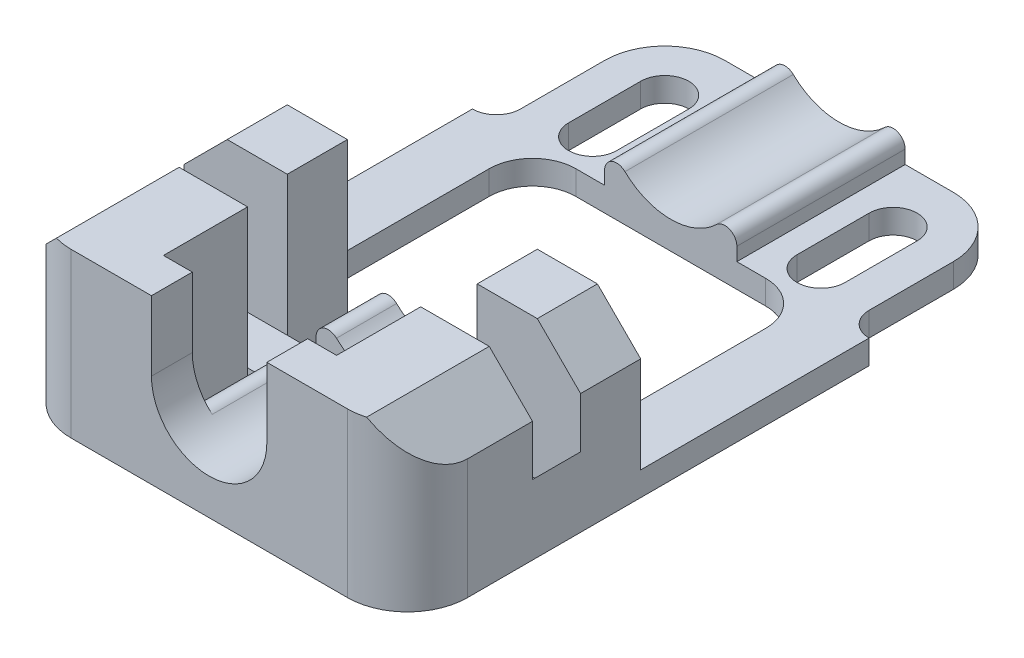
SolidWorks part; units mm, degrees
ref_plane "Front Plane" through (0, 0, 0) normal (0, 0, 1) x (1, 0, 0)
ref_plane "Top Plane" through (0, 0, 0) normal (0, 1, 0) x (1, 0, 0)
ref_plane "Right Plane" through (0, 0, 0) normal (1, 0, 0) x (0, 0, -1)
sketch "Sketch1" plane through (0, 0, 0) normal (0, 1, 0) x (1, 0, 0)
  line L1 (-8.25, 4.85) -> (8.25, 4.85)
  line L2 (-8.25, 4.85) -> (-8.25, -4.85)
  line L3 (-8.25, -4.85) -> (8.25, -4.85)
  line L4 (8.25, 4.85) -> (8.25, -4.85)
  line L5 (-8.25, 4.85) -> (8.25, -4.85) construction
  line L6 (-8.25, -4.85) -> (8.25, 4.85) construction
  point P0 (0, 0)
  dimension "D1" = 16.5
  dimension "D2" = 9.7
extrude "Boss-Extrude1" add sketch "Sketch1" along normal blind 6.8
sketch "Sketch2" plane through (0, 6.8, 0) normal (0, 1, 0) x (1, 0, 0)
  line L0 (-8.25, 1.35) -> (8.25, 1.35) construction
  line L3 (-8.25, 4.85) -> (-8.25, -4.85) construction
  line L4 (-8.25, 2.35) -> (8.25, 2.35)
  line L5 (-8.25, 2.35) -> (-8.25, 0.35)
  line L6 (-8.25, 0.35) -> (8.25, 0.35)
  line L7 (8.25, 2.35) -> (8.25, 0.35)
  line L8 (-8.25, 2.35) -> (8.25, 0.35) construction
  line L9 (-8.25, 0.35) -> (8.25, 2.35) construction
  line L10 (8.25, -4.85) -> (8.25, 4.85) construction
  line L11 (8.25, 4.85) -> (-8.25, 4.85) construction
  line L12 (0, 4.85) -> (0, -4.85) construction
  line L13 (-8.25, -4.85) -> (8.25, -4.85) construction
  point P6 (0, 1.35)
  dimension "D1" = 16.5
  dimension "D2" = 2
  dimension "D3" = 2.5
extrude "Cut-Extrude1" cut sketch "Sketch2" against normal blind 5.8
sketch "Sketch3" plane through (0, 0, -4.85) normal (0, 0, -1) x (-1, 0, 0)
  line L0 (0, 6.8) -> (0, 0) construction
  line L1 (-8.25, 6.8) -> (8.25, 6.8) construction
  line L2 (-8.25, 0) -> (8.25, 0) construction
  line L3 (-8.25, 1) -> (8.25, 1) construction
  line L4 (-8.25, 6.8) -> (-8.25, 0) construction
  line L5 (8.25, 6.8) -> (8.25, 0) construction
  line L6 (-8.25, 1) -> (8.25, 1) construction
  line L7 (-8.25, 6.8) -> (8.25, 1) construction
  line L8 (8.25, 6.8) -> (-8.25, 1) construction
  line L9 (-2.75, 3.9) -> (-2.75, 6.8)
  line L10 (2.75, 3.9) -> (2.75, 6.8)
  circle A0 centre (0, 3.9) radius 2.75
  line M5 (8.25, 6.8) -> (-8.25, 6.8)
  dimension "D1" = 5.5
extrude "Cut-Extrude2" cut sketch "Sketch3" against normal up to next contours A0 | A0 L10 L9 M5 region at (2.6878, 5.35, -4.85) region at (0, 3.9, -4.85)
sketch "Sketch4" plane through (0, 0, 4.85) normal (0, 0, 1) x (1, 0, 0)
  line L0 (0, 0) -> (0, 6.8) construction
  line L1 (-8.25, 6.8) -> (8.25, 6.8) construction
  line L3 (-2.4, 3.9) -> (2.4, 3.9)
  line L4 (-2.4, 3.9) -> (-2.4, 6.8)
  line L5 (-2.4, 6.8) -> (2.4, 6.8)
  line L6 (2.4, 3.9) -> (2.4, 6.8)
  circle A0 centre (0, 3.9) radius 2.4
  arc A1 (-2.75, 3.9) -> (2.75, 3.9) centre (0, 3.9) ccw construction
  line M4 (8.25, 6.8) -> (-8.25, 6.8)
  dimension "D1" = 4.8
extrude "Cut-Extrude3" cut sketch "Sketch4" against normal up to next contours L0 A0 L3 | A0 L0 L3 | L3 L0 A0 | L0 L3 A0 | L0 A0 L6 M4 | A0 L0 L5 L4 region at (-1.0186, 2.8814, 4.85) region at (1.0186, 2.8814, 4.85) region at (-1.0186, 4.9186, 4.85) region at (1.0186, 4.9186, 4.85) region at (-1.5369, 6.1511, 4.85) region at (1.5369, 6.1511, 4.85)
sketch "Sketch5" plane through (0, 6.8, 0) normal (0, 1, 0) x (1, 0, 0)
  line L0 (-2.75, 2.35) -> (-8.25, 2.35) construction
  line L1 (-2.75, 4.85) -> (-3.95, 4.85)
  line L2 (-2.75, 4.85) -> (-2.75, 2.35)
  line L3 (-2.75, 2.35) -> (-3.95, 2.35)
  line L4 (-3.95, 4.85) -> (-3.95, 2.35)
  line L5 (8.25, 2.35) -> (2.75, 2.35) construction
  line L6 (2.75, 4.85) -> (3.95, 4.85)
  line L7 (2.75, 4.85) -> (2.75, 2.35)
  line L8 (2.75, 2.35) -> (3.95, 2.35)
  line L9 (3.95, 4.85) -> (3.95, 2.35)
  line L11 (-2.4, 0.35) -> (-3.6, 0.35)
  line L12 (-2.4, 0.35) -> (-2.4, -3.15)
  line L13 (-2.4, -3.15) -> (-3.6, -3.15)
  line L14 (-3.6, 0.35) -> (-3.6, -3.15)
  line L15 (2.4, 0.35) -> (3.6, 0.35)
  line L16 (2.4, 0.35) -> (2.4, -3.15)
  line L17 (2.4, -3.15) -> (3.6, -3.15)
  line L18 (3.6, 0.35) -> (3.6, -3.15)
  dimension "D1" = 1.2
  dimension "D2" = 3.5
extrude "Cut-Extrude4" cut sketch "Sketch5" against normal through all
sketch "Sketch6" plane through (0, 6.8, 0) normal (0, 1, 0) x (1, 0, 0)
  line L1 (-8.25, -4.85) -> (8.25, -4.85)
  line L2 (-8.25, -4.85) -> (-8.25, 4.85)
  line L3 (-8.25, 4.85) -> (8.25, 4.85)
  line L4 (8.25, -4.85) -> (8.25, 4.85)
extrude "Cut-Extrude5" [suppressed] cut sketch "Sketch6" against normal up to vertex up to point (2.4, 3.9, 3.15)
sketch "Sketch7" plane through (0, 0, -2.35) normal (0, 0, 1) x (1, 0, 0)
  line L0 (-6.35, 1) -> (-8.25, 2.9)
  line L1 (-3.95, 1) -> (-8.25, 1) construction
  line L2 (-8.25, 1) -> (-8.25, 6.8) construction
  line L3 (0, 0) -> (0, 3.9) construction
  line L4 (-8.25, 2.9) -> (-8.25, 1)
  line L5 (-8.25, 6.8) -> (-8.25, 0) construction
  line L6 (-8.25, 1) -> (-6.35, 1)
  line L7 (8.25, 2.9) -> (8.25, 1)
  line L8 (6.35, 1) -> (8.25, 2.9)
  line L9 (8.25, 1) -> (6.35, 1)
  dimension "D1" = 45
  dimension "D2" = 1.9
extrude "Boss-Extrude2" add sketch "Sketch7" along normal up to surface (2 mm away) up to face at (-5.925, 3.9, -0.35)
chamfer "Chamfer1" distance 1.8 angle 45 4 edges at (-8.25, 6.8, -3.6) (-8.25, 6.8, 2.25) (8.25, 6.8, -3.6) (8.25, 6.8, 2.25)
fillet "Fillet4" radius 2.5 2 edges at (8.25, 2.5, 4.85) (-8.25, 2.5, 4.85)
sketch "Sketch8" plane through (0, 0, 0) normal (0, -1, 0) x (1, 0, 0)
  line L0 (-5.75, -18.85) -> (-5.75, -15.85) construction
  line L1 (-3.75, -15.85) -> (-3.75, -18.85) construction
  line L2 (5.75, -18.85) -> (5.75, -15.85) construction
  line L3 (3.75, -15.85) -> (3.75, -18.85) construction
  line L4 (-5.75, -18.85) -> (-5.75, -15.85)
  line L5 (-3.75, -15.85) -> (-3.75, -18.85)
  line L6 (5.75, -18.85) -> (5.75, -15.85)
  line L7 (3.75, -15.85) -> (3.75, -18.85)
  line L8 (-8.25, -4.85) -> (-8.25, -14.35)
  line L9 (8.25, -4.85) -> (8.25, -14.35)
  line L10 (-8.25, -14.35) -> (8.25, -14.35)
  line L11 (-8.25, -4.85) -> (-5.75, -4.85)
  line L12 (78.5, 13.6414) -> (78.5, 114.6586)
  line L13 (48.9288, -14.35) -> (50.5086, -14.35)
  line L14 (45.9288, -15.35) -> (47.9288, -15.35)
  line L15 (8.25, -14.35) -> (44.9288, -14.35)
  line L16 (7.25, -18.85) -> (7.25, -15.35)
  line L17 (-4.75, -21.35) -> (4.75, -21.35)
  line L18 (-7.25, -15.35) -> (-7.25, -18.85)
  line L19 (-44.9288, -14.35) -> (-8.25, -14.35)
  line L20 (-47.9288, -15.35) -> (-45.9288, -15.35)
  line L21 (-50.5086, -14.35) -> (-48.9288, -14.35)
  line L22 (-78.5, 114.6586) -> (-78.5, 13.6414)
  line L23 (50.5086, 142.65) -> (-50.5086, 142.65)
  line L24 (78.5, 13.6414) -> (78.5, 114.6586)
  line L25 (48.9288, -14.35) -> (50.5086, -14.35)
  line L26 (45.9288, -15.35) -> (47.9288, -15.35)
  line L27 (8.25, -14.35) -> (44.9288, -14.35)
  line L28 (7.25, -18.85) -> (7.25, -15.35)
  line L29 (-4.75, -21.35) -> (4.75, -21.35)
  line L30 (-7.25, -15.35) -> (-7.25, -18.85)
  line L31 (-44.9288, -14.35) -> (-8.25, -14.35)
  line L32 (-47.9288, -15.35) -> (-45.9288, -15.35)
  line L33 (-50.5086, -14.35) -> (-48.9288, -14.35)
  line L34 (-78.5, 114.6586) -> (-78.5, 13.6414)
  line L35 (50.5086, 142.65) -> (-50.5086, 142.65)
  line L36 (-8.25, -4.85) -> (-8.25, -15.85)
  line L37 (-8.25, -15.85) -> (-5.75, -15.85)
  line L38 (-5.75, -4.85) -> (-5.75, -15.85)
  line L39 (8.25, -4.85) -> (5.75, -4.85)
  line L40 (8.25, -4.85) -> (8.25, -15.85)
  line L41 (8.25, -15.85) -> (5.75, -15.85)
  line L42 (5.75, -4.85) -> (5.75, -15.85)
  arc A0 (-5.75, -18.85) -> (-3.75, -18.85) centre (-4.75, -18.85) ccw construction
  arc A1 (-3.75, -15.85) -> (-5.75, -15.85) centre (-4.75, -15.85) ccw construction
  arc A2 (3.75, -18.85) -> (5.75, -18.85) centre (4.75, -18.85) ccw construction
  arc A3 (5.75, -15.85) -> (3.75, -15.85) centre (4.75, -15.85) ccw construction
  arc A4 (-5.75, -18.85) -> (-3.75, -18.85) centre (-4.75, -18.85) ccw
  arc A5 (-3.75, -15.85) -> (-5.75, -15.85) centre (-4.75, -15.85) ccw
  arc A6 (3.75, -18.85) -> (5.75, -18.85) centre (4.75, -18.85) ccw
  arc A7 (5.75, -15.85) -> (3.75, -15.85) centre (4.75, -15.85) ccw
  arc A20 (78.7927, 115.3655) -> (51.2155, 142.9427) centre (65, 129.15) ccw
  arc A21 (78.7927, 115.3655) -> (78.5, 114.6586) centre (79.5, 114.6586) ccw
  arc A22 (78.5, 13.6414) -> (78.7927, 12.9345) centre (79.5, 13.6414) ccw
  arc A23 (51.2155, -14.6427) -> (78.7927, 12.9345) centre (65, -0.85) ccw
  arc A24 (51.2155, -14.6427) -> (50.5086, -14.35) centre (50.5086, -15.35) ccw
  arc A25 (48.9288, -14.35) -> (47.9288, -15.35) centre (48.9288, -15.35) ccw
  arc A26 (45.9288, -15.35) -> (44.9288, -14.35) centre (44.9288, -15.35) ccw
  arc A27 (8.25, -14.35) -> (7.25, -15.35) centre (8.25, -15.35) ccw
  arc A28 (4.75, -21.35) -> (7.25, -18.85) centre (4.75, -18.85) ccw
  arc A29 (-7.25, -18.85) -> (-4.75, -21.35) centre (-4.75, -18.85) ccw
  arc A30 (-7.25, -15.35) -> (-8.25, -14.35) centre (-8.25, -15.35) ccw
  arc A31 (-44.9288, -14.35) -> (-45.9288, -15.35) centre (-44.9288, -15.35) ccw
  arc A32 (-47.9288, -15.35) -> (-48.9288, -14.35) centre (-48.9288, -15.35) ccw
  arc A33 (-50.5086, -14.35) -> (-51.2155, -14.6427) centre (-50.5086, -15.35) ccw
  arc A34 (-78.7927, 12.9345) -> (-51.2155, -14.6427) centre (-65, -0.85) ccw
  arc A35 (-78.7927, 12.9345) -> (-78.5, 13.6414) centre (-79.5, 13.6414) ccw
  arc A36 (-78.5, 114.6586) -> (-78.7927, 115.3655) centre (-79.5, 114.6586) ccw
  arc A37 (-51.2155, 142.9427) -> (-78.7927, 115.3655) centre (-65, 129.15) ccw
  arc A38 (-51.2155, 142.9427) -> (-50.5086, 142.65) centre (-50.5086, 143.65) ccw
  arc A39 (50.5086, 142.65) -> (51.2155, 142.9427) centre (50.5086, 143.65) ccw
  arc A40 (78.7927, 115.3655) -> (51.2155, 142.9427) centre (65, 129.15) ccw
  arc A41 (78.7927, 115.3655) -> (78.5, 114.6586) centre (79.5, 114.6586) ccw
  arc A42 (78.5, 13.6414) -> (78.7927, 12.9345) centre (79.5, 13.6414) ccw
  arc A43 (51.2155, -14.6427) -> (78.7927, 12.9345) centre (65, -0.85) ccw
  arc A44 (51.2155, -14.6427) -> (50.5086, -14.35) centre (50.5086, -15.35) ccw
  arc A45 (48.9288, -14.35) -> (47.9288, -15.35) centre (48.9288, -15.35) ccw
  arc A46 (45.9288, -15.35) -> (44.9288, -14.35) centre (44.9288, -15.35) ccw
  arc A47 (8.25, -14.35) -> (7.25, -15.35) centre (8.25, -15.35) ccw
  arc A48 (4.75, -21.35) -> (7.25, -18.85) centre (4.75, -18.85) ccw
  arc A49 (-7.25, -18.85) -> (-4.75, -21.35) centre (-4.75, -18.85) ccw
  arc A50 (-7.25, -15.35) -> (-8.25, -14.35) centre (-8.25, -15.35) ccw
  arc A51 (-44.9288, -14.35) -> (-45.9288, -15.35) centre (-44.9288, -15.35) ccw
  arc A52 (-47.9288, -15.35) -> (-48.9288, -14.35) centre (-48.9288, -15.35) ccw
  arc A53 (-50.5086, -14.35) -> (-51.2155, -14.6427) centre (-50.5086, -15.35) ccw
  arc A54 (-78.7927, 12.9345) -> (-51.2155, -14.6427) centre (-65, -0.85) ccw
  arc A55 (-78.7927, 12.9345) -> (-78.5, 13.6414) centre (-79.5, 13.6414) ccw
  arc A56 (-78.5, 114.6586) -> (-78.7927, 115.3655) centre (-79.5, 114.6586) ccw
  arc A57 (-51.2155, 142.9427) -> (-78.7927, 115.3655) centre (-65, 129.15) ccw
  arc A58 (-51.2155, 142.9427) -> (-50.5086, 142.65) centre (-50.5086, 143.65) ccw
  arc A59 (50.5086, 142.65) -> (51.2155, 142.9427) centre (50.5086, 143.65) ccw
  line M38 (-8.25, -4.85) -> (-3.95, -4.85)
  line M46 (3.95, -4.85) -> (8.25, -4.85)
  dimension "D1" = 0
extrude "Boss-Extrude3" add sketch "Sketch8" against normal blind 1 contours L38 L8 L10 M38 | L42 L10 L9 M46 | A47 L10 L42 L41 L28 | A50 L30 L37 L38 L10 | L30 A49 L29 A48 L28 L41 L6 A6 L7 A7 L42 L10 L38 A5 L5 A4 L4 L37 region at (0, 0, -18.0292) region at (-6.5848, 0, -15.0541) region at (-7, 0, -9.6) region at (7, 0, -9.6) region at (6.5848, 0, -15.0541)
fillet "Fillet5" radius 1.8 4 edges at (5.75, 0.5, -14.35) (-5.75, 0.5, -14.35) (5.75, 0.5, -4.85) (-5.75, 0.5, -4.85)
sketch "Sketch11" plane through (0, 0, -21.35) normal (0, 0, -1) x (-1, 0, 0)
  line L0 (0, 0) -> (0, 1) construction
  line L1 (4.75, 1) -> (-4.75, 1) construction
  line L2 (0, 3.9) -> (0, 1) construction
  line L3 (2.75, 3.9) -> (-2.75, 3.9)
  line L4 (2.75, 3.9) -> (2.75, 1)
  line L5 (2.75, 1) -> (-2.75, 1)
  line L6 (-2.75, 3.9) -> (-2.75, 1)
  line L7 (2.75, 3.9) -> (-2.75, 1) construction
  line L8 (2.75, 1) -> (-2.75, 3.9) construction
  line L9 (-2.75, 3.9) -> (2.75, 3.9) construction
  circle A0 centre (0, 3.9) radius 2.75
  arc A1 (-2.4, 3.9) -> (2.4, 3.9) centre (0, 3.9) ccw construction
  point P5 (0, 2.45)
  line M8 (4.75, 1) -> (-4.75, 1)
  dimension "D1" = 5.5
extrude "Boss-Extrude5" add sketch "Sketch11" against normal up to surface (7 mm away) contours A0 L6 L4 M8 region at (-2.6878, 2.45, -21.35) up to face at (0, 0.5, -14.35)
fillet "Fillet1" radius 0.5 6 edges at (2.4, 3.9, 1.4) (-2.4, 3.9, 1.4) (-2.75, 3.9, -3.6) (2.75, 3.9, -3.6) (-2.75, 3.9, -17.85) (2.75, 3.9, -17.85)
